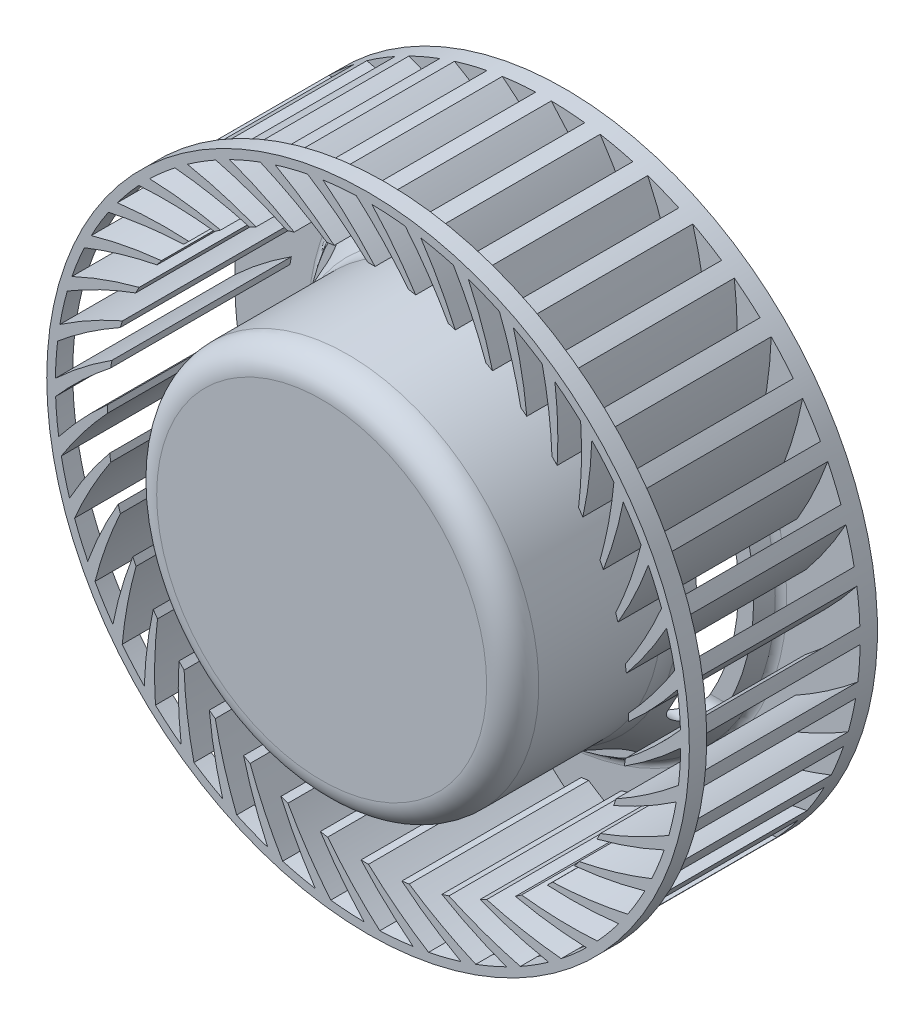
SolidWorks part; units mm, degrees
ref_plane "Front Plane" through (0, 0, 0) normal (0, 0, 1) x (1, 0, 0)
ref_plane "Top Plane" through (0, 0, 0) normal (0, 1, 0) x (1, 0, 0)
ref_plane "Right Plane" through (0, 0, 0) normal (1, 0, 0) x (0, 0, -1)
sketch "Sketch2" plane through (0, 0, 0) normal (1, 0, 0) x (0, 0, -1)
  line L0 (-0.9091, 16.3636) -> (0, 16.3636)
  line L31 (-0.9091, 15.7895) -> (-10.9081, 15.7895) construction
  line L32 (-10.9081, 15.7895) -> (-10.9081, 16.8182) construction
  line L33 (-10.9081, 16.8182) -> (-9.999, 16.8182) construction
  line L34 (-9.999, 16.8182) -> (-9.999, 16.3636) construction
  line L35 (-9.999, 16.3636) -> (-0.9091, 16.3636) construction
  line L36 (0, 16.3636) -> (0, 12.25)
  line L37 (0, 12.25) -> (-0.2606, 12.25)
  line L38 (-0.7615, 11.5595) -> (-3.8509, 9.629)
  line L40 (-4.2122, 10.2072) -> (-1.1228, 12.1377)
  line L41 (-0.9091, 12.5232) -> (-0.9091, 16.3636)
  line L46 (-4.9348, 9.3182) -> (-11.3626, 9.3182)
  line L47 (-12.0444, 8.6364) -> (-12.0444, 0)
  line L53 (-12.7262, 0) -> (-12.7262, 8.6364)
  line L55 (-4.9348, 10) -> (-11.3626, 10)
  line L56 (0, 0) -> (-12.0444, 0) construction
  line L57 (-12.0444, 0) -> (-12.7262, 0)
  arc A10 (-0.7615, 11.5595) -> (-0.2606, 12.25) centre (-1.3636, 12.5232) ccw
  arc A11 (-1.1228, 12.1377) -> (-0.9091, 12.5232) centre (-1.3636, 12.5232) ccw
  arc A12 (-4.9348, 9.3182) -> (-3.8509, 9.629) centre (-4.9348, 11.3636) ccw
  arc A13 (-11.3626, 9.3182) -> (-12.0444, 8.6364) centre (-11.3626, 8.6364) ccw
  arc A15 (-11.3626, 10) -> (-12.7262, 8.6364) centre (-11.3626, 8.6364) ccw
  arc A19 (-4.9348, 10) -> (-4.2122, 10.2072) centre (-4.9348, 11.3636) ccw
  dimension "D1" = 0.6818
  dimension "D2" = 20
  dimension "D3" = 32
  dimension "D4" = 24.5
  dimension "D5" = 16.3636
  dimension "D6" = 16.8182
  dimension "D7" = 0.9091
  dimension "D8" = 10.9081
  dimension "D9" = 0.5741
  dimension "D10" = 0.2606
  dimension "D11" = 0.9091
revolve "Revolve1" add sketch "Sketch2" angle 360 about L56
sketch "Sketch3" plane through (0, 0, 0) normal (1, 0, 0) x (0, 0, -1)
  line L2 (0, -16.3636) -> (0, 16.3636) construction
  line L3 (-1.8182, -5.4545) -> (-1.8182, 5.4545)
  line L5 (-3.6364, 5.4545) -> (-3.6364, -5.4545)
  arc A0 (-1.8182, 5.4545) -> (-3.6364, 5.4545) centre (-2.7273, 5.4545) ccw
  arc A1 (-3.6364, -5.4545) -> (-1.8182, -5.4545) centre (-2.7273, -5.4545) ccw
  point P2 (-1.8182, 0)
  dimension "D1" = 1.8182
  dimension "D2" = 1.8182
  dimension "D3" = 10.9091
extrude "Cut-Extrude2" cut sketch "Sketch3" against normal up to next and the other way up to next
pattern_circular "CirPattern1" count 2 over 90 of "Cut-Extrude2"
sketch "Sketch4" plane through (0, 0, 0.9091) normal (0, 0, 1) x (1, 0, 0)
  line L0 (0, 0) -> (23.1414, 0) construction
  line L1 (0, 0) -> (13.4718, -2.112) construction
  line L2 (13.4063, -2.4944) -> (0, 0) construction
  line L3 (0, 0) -> (16.3624, -0.2014) construction
  line L4 (16.3521, 0.6153) -> (0, 0) construction
  arc A5 (13.4718, -2.112) -> (16.3521, 0.6153) centre (0, 15) ccw
  arc A6 (13.4063, -2.4944) -> (16.3624, -0.2014) centre (2.3465, 14.8153) ccw
  arc A7 (13.4063, -2.4944) -> (13.4718, -2.112) centre (0, 0) ccw
  arc A8 (16.3624, -0.2014) -> (16.3521, 0.6153) centre (0, 0) ccw
  dimension "D1" = 21.7786
  dimension "D2" = 20.5413
  dimension "D3" = 13.6364
  dimension "D4" = 16.3636
  dimension "D5" = 2.155
  dimension "D6" = 11.065
  dimension "D7" = 9.835
  dimension "D8" = 0.705
extrude "Boss-Extrude1" add sketch "Sketch4" along normal blind 9.39
pattern_circular "CirPattern2" count 40 over 360 about axis through (0, 0, 0.9091) along (0, 0, -1) of "Boss-Extrude1"
sketch "Sketch5" plane through (0, 0, 10.2991) normal (0, 0, 1) x (1, 0, 0)
  circle A0 centre (0, 0) radius 16.8182
  circle A1 centre (0, 0) radius 16.3636
  dimension "D1" = 32.7273
  dimension "D2" = 33.6364
extrude "Boss-Extrude2" add sketch "Sketch5" against normal blind 0.9091
